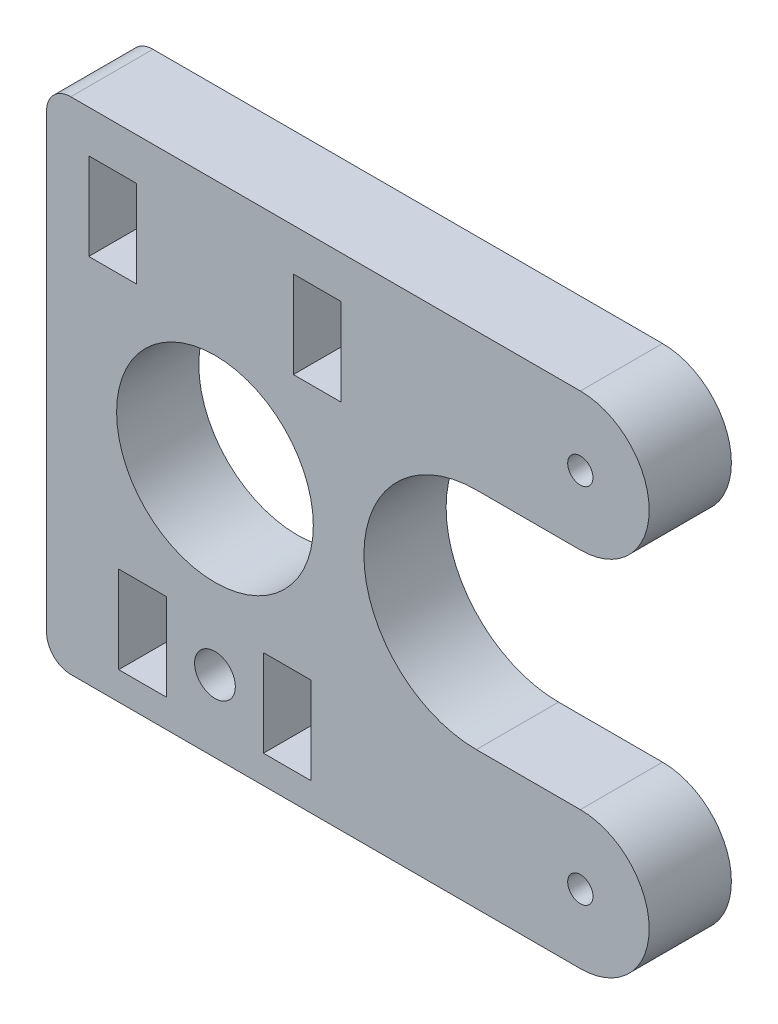
SolidWorks part; units mm, degrees
material "Acrylic (Medium-high impact)"
ref_plane "Front Plane" through (0, 0, 0) normal (0, 0, 1) x (1, 0, 0)
ref_plane "Top Plane" through (0, 0, 0) normal (0, 1, 0) x (1, 0, 0)
ref_plane "Right Plane" through (0, 0, 0) normal (1, 0, 0) x (0, 0, -1)
sketch "Sketch1" plane through (0, 0, 0) normal (0, 0, 1) x (1, 0, 0)
  line L0 (669.2168, 348.5655) -> (648.4638, 348.5655)
  line L1 (646.7465, 346.8482) -> (646.7465, 314.6828)
  line L2 (648.4638, 312.9655) -> (669.2168, 312.9655)
  line L3 (653.1465, 339.3655) -> (653.1465, 345.5655)
  line L4 (653.1465, 345.5655) -> (649.7465, 345.5655)
  line L5 (649.7465, 345.5655) -> (649.7465, 339.3655)
  line L6 (649.7465, 339.3655) -> (653.1465, 339.3655)
  line L7 (651.8765, 314.9655) -> (655.2765, 314.9655)
  line L8 (655.2765, 314.9655) -> (655.2765, 321.1655)
  line L9 (655.2765, 321.1655) -> (651.8765, 321.1655)
  line L10 (651.8765, 321.1655) -> (651.8765, 314.9655)
  line L11 (667.7065, 339.3655) -> (667.7065, 345.5655)
  line L12 (667.7065, 345.5655) -> (664.3065, 345.5655)
  line L13 (664.3065, 345.5655) -> (664.3065, 339.3655)
  line L14 (664.3065, 339.3655) -> (667.7065, 339.3655)
  line L15 (662.1765, 321.1655) -> (662.1765, 314.9655)
  line L16 (662.1765, 314.9655) -> (665.5765, 314.9655)
  line L17 (665.5765, 314.9655) -> (665.5765, 321.1655)
  line L18 (665.5765, 321.1655) -> (662.1765, 321.1655)
  line L19 (-318.4867, 330.7655) -> (49681.5133, 330.7655) construction
  line L21 (653.1465, 339.3655) -> (664.3065, 339.3655) construction
  line L22 (657.2765, 318.0655) -> (655.2765, 318.0655) construction
  line L23 (660.1765, 318.0655) -> (662.1765, 318.0655) construction
  line L24 (658.7265, -664.8306) -> (658.7265, 49335.1694) construction
  line L25 (669.2168, 312.9655) -> (684.7265, 312.9655)
  line L26 (669.2168, 348.5655) -> (684.7265, 348.5655)
  line L27 (684.7265, 317.8655) -> (684.7265, 330.7655) construction
  line L28 (684.7265, 330.7655) -> (684.7265, 343.6655) construction
  line L29 (684.7265, -669.3722) -> (684.7265, 49330.6278) construction
  line L30 (662.1765, 330.7655) -> (662.1765, 348.5655) construction
  line L31 (662.1765, 330.7655) -> (662.1765, 312.9655) construction
  line L32 (684.7265, 338.7655) -> (677.3265, 338.7655)
  line L33 (684.7265, 322.7655) -> (677.3265, 322.7655)
  circle A0 centre (684.7265, 343.6655) radius 0.9
  circle A1 centre (684.7265, 317.8655) radius 0.9
  arc A2 (684.7265, 312.9655) -> (684.7265, 322.7655) centre (684.7265, 317.8655) ccw
  circle A3 centre (658.7265, 318.0655) radius 1.45
  arc A4 (648.4638, 348.5655) -> (646.7465, 346.8482) centre (648.4638, 346.8482) ccw
  arc A5 (684.7265, 348.5655) -> (684.7265, 338.7655) centre (684.7265, 343.6655) cw
  arc A6 (677.3265, 338.7655) -> (677.3265, 322.7655) centre (677.3265, 330.7655) ccw
  arc A7 (646.7465, 314.6828) -> (648.4638, 312.9655) centre (648.4638, 314.6828) ccw
  circle A8 centre (658.7265, 330.7655) radius 7
  point P27 (658.7265, 339.3655)
  point P38 (669.3265, 330.7655)
  point P39 (665.7265, 330.7655)
  dimension "D5" = 2.9
  dimension "D12" = 3.6
  dimension "D13" = 14
  dimension "D14" = 1.8
  dimension "D15" = 1.7173
  dimension "D10" = 26
  dimension "D1" = 2
  dimension "D2" = 6.2
  dimension "D3" = 3.4
  dimension "D4" = 3.4
  dimension "D6" = 11.16
  dimension "D7" = 3
  dimension "D8" = 3
  dimension "D9" = 2
  dimension "D11" = 12.9
  dimension "D17" = 18.2
extrude "Boss-Extrude2" add sketch "Sketch1" along normal blind 5.85
